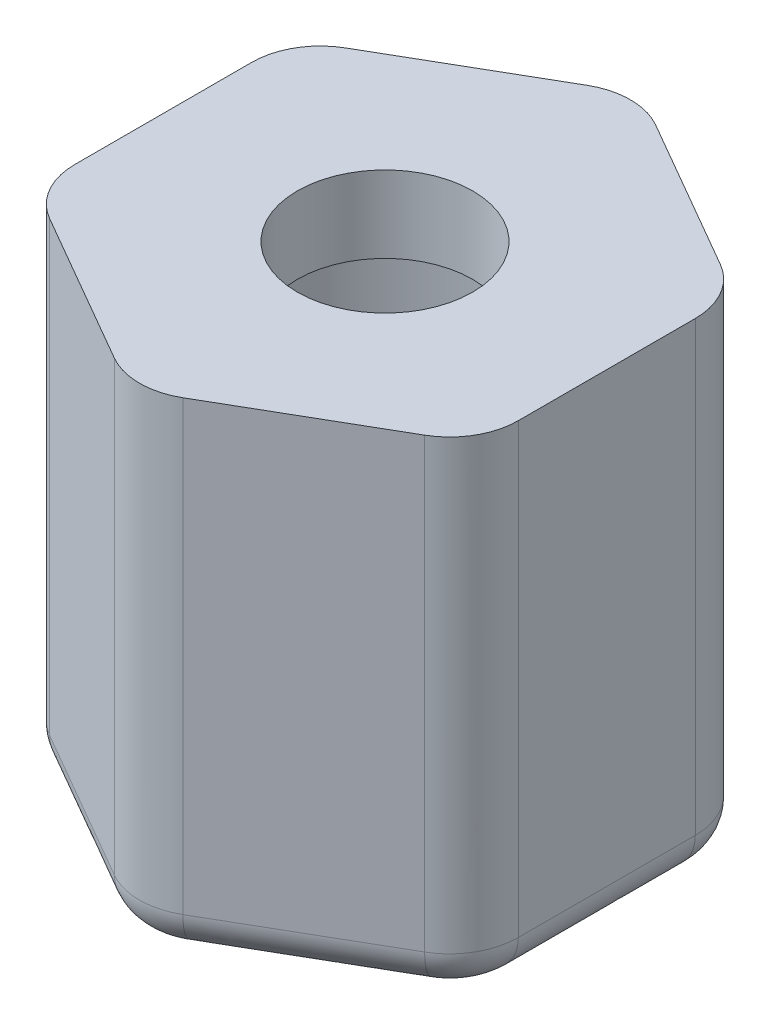
SolidWorks part; units mm, degrees
ref_plane "Front Plane" through (0, 0, 0) normal (0, 0, 1) x (1, 0, 0)
ref_plane "Top Plane" through (0, 0, 0) normal (0, 1, 0) x (1, 0, 0)
ref_plane "Right Plane" through (0, 0, 0) normal (1, 0, 0) x (0, 0, -1)
sketch "Sketch1" plane through (0, 0, 0) normal (0, 1, 0) x (1, 0, 0)
  line L1 (0, 12.7017) -> (-11, 6.3509)
  line L2 (-11, 6.3509) -> (-11, -6.3509)
  line L3 (-11, -6.3509) -> (0, -12.7017)
  line L4 (0, -12.7017) -> (11, -6.3509)
  line L5 (11, -6.3509) -> (11, 6.3509)
  line L6 (11, 6.3509) -> (0, 12.7017)
  circle A0 centre (0, 0) radius 11 construction
extrude "Boss-Extrude1" add sketch "Sketch1" along normal blind 24.2
sketch "Sketch3" plane through (0, 24.2, 0) normal (0, 1, 0) x (1, 0, 0)
  circle A0 centre (0, 0) radius 8.85
  dimension "D1" = 17.7
extrude "Cut-Extrude1" cut sketch "Sketch3" against normal blind 24.2
sketch "Sketch4" plane through (0, 24.2, 0) normal (0, 1, 0) x (1, 0, 0)
  line L0 (-11, 6.3509) -> (-11, -6.3509) construction
  line L1 (-11, -6.3509) -> (0, -12.7017) construction
  line L2 (0, -12.7017) -> (11, -6.3509) construction
  line L3 (11, -6.3509) -> (11, 6.3509) construction
  line L4 (11, 6.3509) -> (0, 12.7017) construction
  line L5 (0, 12.7017) -> (-11, 6.3509) construction
  line L6 (-11, 6.3509) -> (-11, -6.3509)
  line L7 (-11, -6.3509) -> (0, -12.7017)
  line L8 (0, -12.7017) -> (11, -6.3509)
  line L9 (11, -6.3509) -> (11, 6.3509)
  line L10 (11, 6.3509) -> (0, 12.7017)
  line L11 (0, 12.7017) -> (-11, 6.3509)
  circle A0 centre (0, 0) radius 4.35
  dimension "D1" = 8.7
extrude "Boss-Extrude2" add sketch "Sketch4" against normal blind 3.8
fillet "Fillet1" radius 3.4 6 edges at (-11, 12.1, -6.3509) (-11, 12.1, 6.3509) (0, 12.1, 12.7017) (11, 12.1, 6.3509) (11, 12.1, -6.3509) (0, 12.1, -12.7017)
fillet "Fillet2" radius 2 12 edges at (-10.5445, 0, -6.0879) (-11, 0, 0) (-10.5445, 0, 6.0879) (-5.5, 0, 9.5263) (0, 0, 12.1757) (5.5, 0, 9.5263) (10.5445, 0, 6.0879) (11, 0, 0) (10.5445, 0, -6.0879) (5.5, 0, -9.5263) (0, 0, -12.1757) (-5.5, 0, -9.5263) tangent propagation no first distance on face at (0, 0, 8.85)
